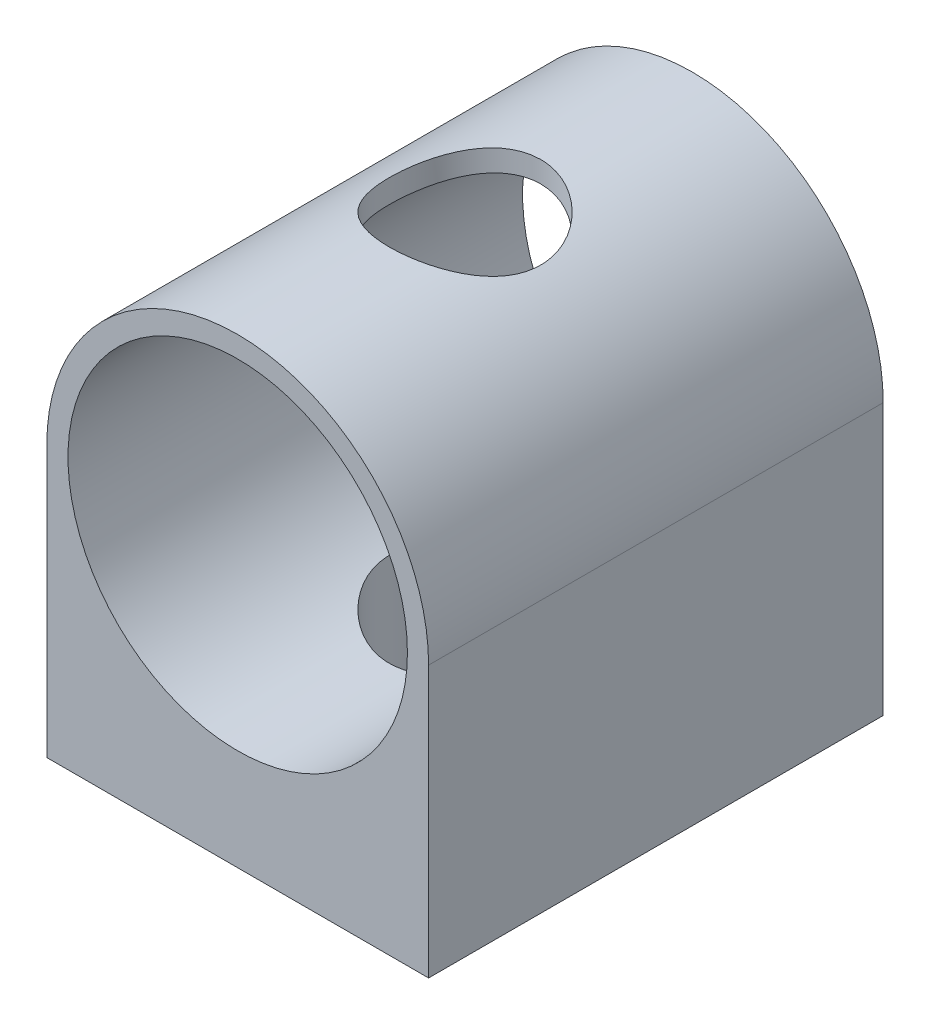
SolidWorks part; units mm, degrees
ref_plane "Front Plane" through (0, 0, 0) normal (0, 0, 1) x (1, 0, 0)
ref_plane "Top Plane" through (0, 0, 0) normal (0, 1, 0) x (1, 0, 0)
ref_plane "Right Plane" through (0, 0, 0) normal (1, 0, 0) x (0, 0, -1)
sketch "Sketch1" plane through (0, 0, 0) normal (0, 0, 1) x (1, 0, 0)
  line L0 (16, 0) -> (-16, 0)
  line L1 (-16, 0) -> (-16, 22.7096)
  line L2 (16, 0) -> (16, 22.7096)
  line L3 (-16, 22.7096) -> (16, 22.7096) construction
  arc A0 (-16, 22.7096) -> (16, 22.7096) centre (0, 22.7096) cw
  circle A1 centre (0, 22.7096) radius 14.224
  point P4 (0, 0)
  point P9 (0, 38.7096)
  dimension "D3" = 28.448
  dimension "D1" = 32
  dimension "D2" = 38.7096
extrude "Boss-Extrude1" add sketch "Sketch1" along normal blind 38.1 contours L3 L1 L0 L2 A1 | A0 L3 A1 region at (0, 7.2216, 0) region at (15.112, 23.0674, 0)
sketch "Sketch2" plane through (0, 0, 0) normal (0, -1, 0) x (1, 0, 0)
  line L0 (0, 38.1) -> (0, 0) construction
  line L1 (16, 38.1) -> (-16, 38.1) construction
  line L2 (16, 19.05) -> (-16, 19.05) construction
  line L3 (16, 38.1) -> (16, 0) construction
  line L4 (-16, 38.1) -> (-16, 0) construction
  circle A0 centre (0, 19.05) radius 6.35
  point P14 (0, 19.05)
  dimension "D1" = 12.7
extrude "Cut-Extrude1" cut sketch "Sketch2" against normal through all
